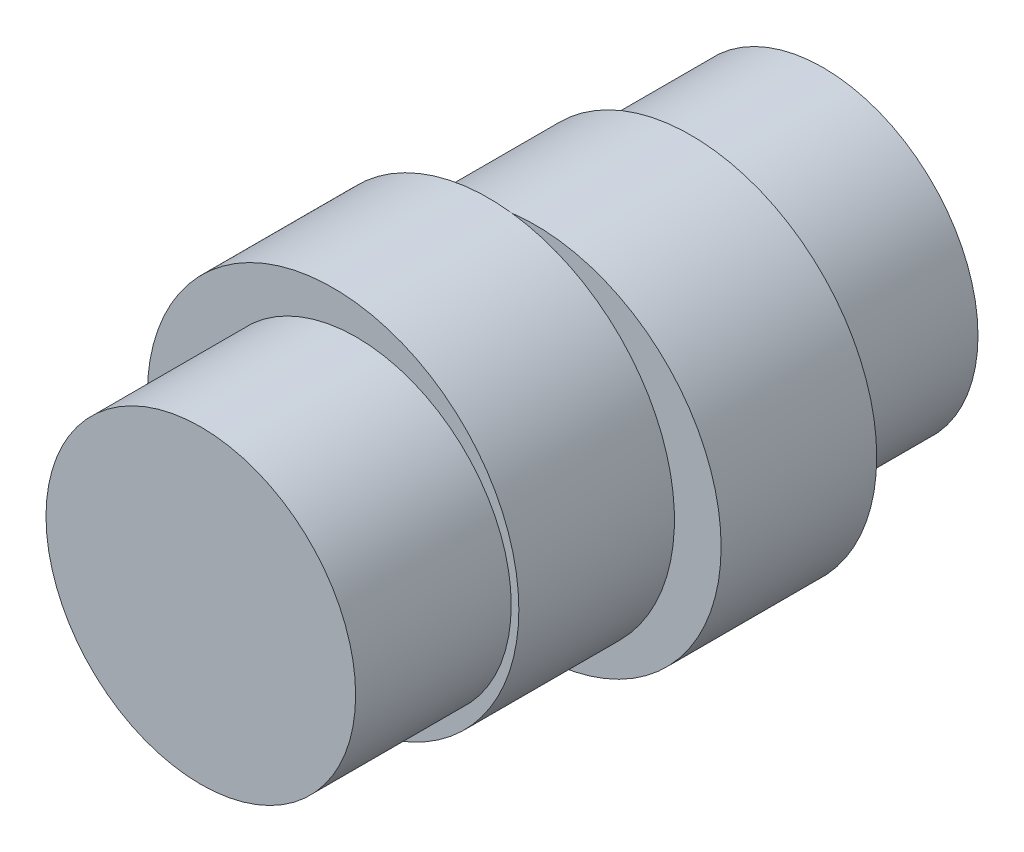
SolidWorks part; units mm, degrees
ref_plane "Front Plane" through (0, 0, 0) normal (0, 0, 1) x (1, 0, 0)
ref_plane "Top Plane" through (0, 0, 0) normal (0, 1, 0) x (1, 0, 0)
ref_plane "Right Plane" through (0, 0, 0) normal (1, 0, 0) x (0, 0, -1)
sketch "Sketch2" plane through (0, 0, 10.0549) normal (0, 0, 1) x (1, 0, 0)
  line L0 (2, 1.5) -> (2, -1.5)
  arc A0 (2, 1.5) -> (2, -1.5) centre (0, 0) ccw
  circle A1 centre (0, 0) radius 4.975
extrude "Boss-Extrude1" add sketch "Sketch2" along normal up to surface (5 mm away)
sketch "Sketch3" plane through (0, 0, 15.0549) normal (0, 0, 1) x (1, 0, 0)
  line L0 (2, 1.5) -> (2, -1.5)
  circle A0 centre (0.75, 0) radius 5.97
  arc A1 (2, 1.5) -> (2, -1.5) centre (0, 0) ccw
  point P0 (0.75, 0)
extrude "Boss-Extrude2" add sketch "Sketch3" along normal blind 5
sketch "Sketch5" plane through (0, 0, 20.0549) normal (0, 0, 1) x (1, 0, 0)
  line L0 (2, 1.5) -> (2, -1.5)
  arc A1 (2, 1.5) -> (2, -1.5) centre (0, 0) ccw
  circle A3 centre (-0.75, 0) radius 5.97
  point P0 (-0.75, 0)
extrude "Boss-Extrude3" add sketch "Sketch5" along normal blind 5
sketch "Sketch6" plane through (0, 0, 25.0549) normal (0, 0, 1) x (1, 0, 0)
  line L0 (2, 1.5) -> (2, -1.5)
  circle A0 centre (0, 0) radius 4.975
  arc A1 (2, 1.5) -> (2, -1.5) centre (0, 0) ccw
extrude "Boss-Extrude4" add sketch "Sketch6" along normal blind 5
sketch "Sketch8" plane through (0, 0, 25.4549) normal (0, 0, 1) x (1, 0, 0)
  circle A1 centre (0, 0) radius 2.6981
extrude "Boss-Extrude5" add sketch "Sketch8" along normal up to surface (4.6 mm away) up to face at (4.975, 0, 30.0549)
sketch "Sketch10" plane through (0, 0, 10.0549) normal (0, 0, -1) x (-1, 0, 0)
  line L7 (-2.2, 1.5652) -> (-2.2, -1.5652)
  arc A1 (-2.2, -1.5652) -> (-2.2, 1.5652) centre (0, 0) ccw
extrude "Cut-Extrude3" cut sketch "Sketch10" against normal blind 16.1
sketch "Sketch12" plane through (0, 0, 10.0549) normal (0, 0, -1) x (-1, 0, 0)
  circle A1 centre (0, 0) radius 2.7
extrude "Cut-Extrude4" cut sketch "Sketch12" against normal blind 3
